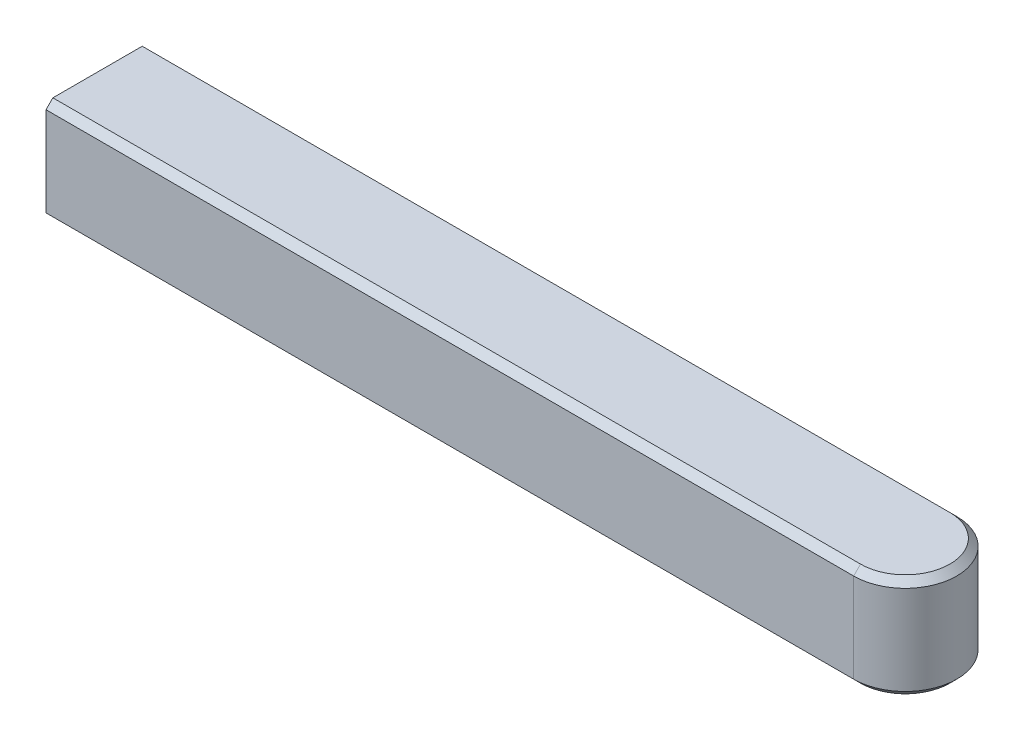
SolidWorks part; units mm, degrees
material "S45C"
ref_plane "Front Plane" through (0, 0, 0) normal (0, 0, 1) x (1, 0, 0)
ref_plane "Top Plane" through (0, 0, 0) normal (0, 1, 0) x (1, 0, 0)
ref_plane "Right Plane" through (0, 0, 0) normal (1, 0, 0) x (0, 0, -1)
sketch "Sketch1" plane through (0, 0, 0) normal (0, 1, 0) x (1, 0, 0)
  line L0 (-12.5, 0) -> (12.5, 0) construction
  line L1 (0, 1.5) -> (0, -1.5) construction
  line L3 (-12.5, 1.5) -> (12.5, 1.5)
  line L4 (-12.5, 1.5) -> (-12.5, -1.5)
  line L5 (-12.5, -1.5) -> (12.5, -1.5)
  line L6 (12.5, 1.5) -> (12.5, -1.5)
  dimension "L" = 25
  dimension "B" = 3
extrude "Boss-Extrude1" add sketch "Sketch1" along normal blind 3
chamfer "Chamfer1" [suppressed] distance 0.2 angle 45
fillet "Fillet1" [suppressed] type full round
fillet "Fillet2" 2 edges at (12.5, 1.5, 1.5) (12.5, 1.5, -1.5) type full round first side face at (0, 1.5, 1.5) second side face at (0, 1.5, -1.5) middle face at (12.5, 1.5, 0)
chamfer "Chamfer2" distance 0.2 angle 45 6 edges at (-0.75, 0, -1.5) (12.5, 0, 0) (-0.75, 0, 1.5) (-0.75, 3, -1.5) (12.5, 3, 0) (-0.75, 3, 1.5)
